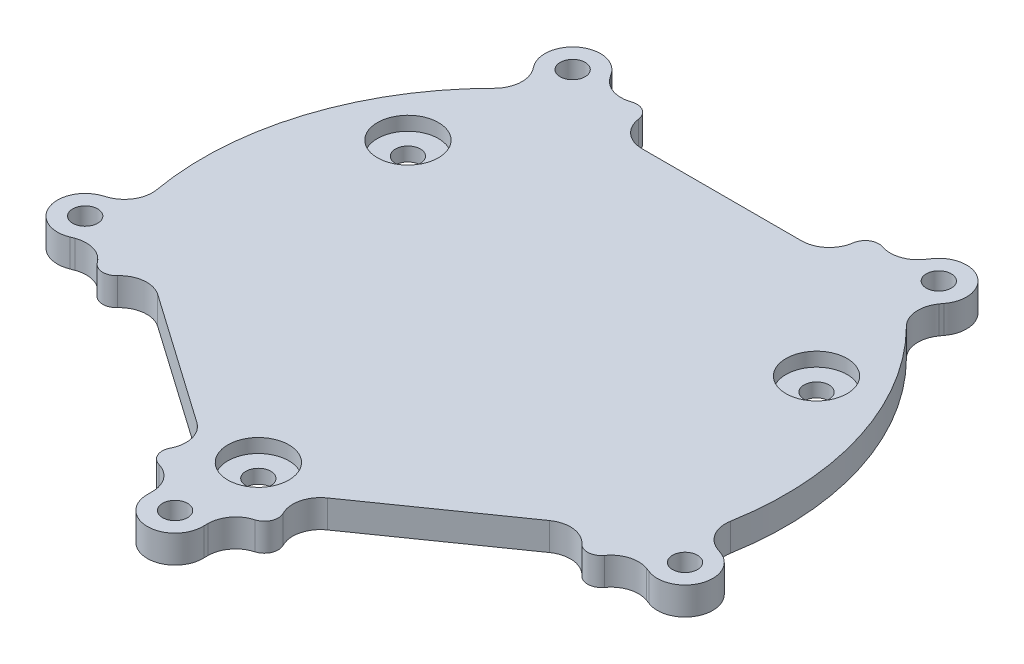
SolidWorks part; units mm, degrees
ref_plane "Plan de face" through (0, 0, 0) normal (0, 0, 1) x (1, 0, 0)
ref_plane "Plan de dessus" through (0, 0, 0) normal (0, 1, 0) x (1, 0, 0)
ref_plane "Plan de droite" through (0, 0, 0) normal (1, 0, 0) x (0, 0, -1)
sketch "Sketch1" plane through (0, 0, 0) normal (0, 1, 0) x (1, 0, 0)
  line L0 (0, 0) -> (0, 41) construction
  line L1 (0, 0) -> (-23.5166, -33.5852) construction
  line L2 (0, 0) -> (23.5166, -33.5852) construction
  line L3 (-39.3263, -22.5152) -> (-7.707, -44.6553)
  line L4 (7.707, -44.6553) -> (39.3263, -22.5152)
  line L5 (-19.3, 41) -> (19.3, 41)
  line L6 (-19.3, 41) -> (-19.3, 48.8238)
  line L8 (19.3, 41) -> (19.3, 48.8238)
  line L9 (7.707, -44.6553) -> (12.1945, -51.0641)
  line L11 (39.3263, -22.5152) -> (43.8138, -28.9241)
  line L12 (-7.707, -44.6553) -> (-12.1945, -51.0641)
  line L13 (-39.3263, -22.5152) -> (-43.8138, -28.9241)
  line L14 (0, 0) -> (0, -42.5) construction
  line L15 (0, 0) -> (-36.8061, 21.25) construction
  line L16 (0, 0) -> (36.8061, 21.25) construction
  arc A0 (-19.3, 48.8238) -> (-43.8138, -28.9241) centre (0, 0) ccw
  arc A1 (43.8138, -28.9241) -> (19.3, 48.8238) centre (0, 0) ccw
  circle A3 centre (-36.8061, 21.25) radius 2.25 construction
  circle A4 centre (36.8061, 21.25) radius 2.25 construction
  circle A6 centre (0, -42.5) radius 2.25 construction
  arc A7 (-12.1945, -51.0641) -> (12.1945, -51.0641) centre (0, 0) ccw
  circle A8 centre (-36.8061, 21.25) radius 5.5
  circle A9 centre (36.8061, 21.25) radius 5.5
  circle A10 centre (0, -42.5) radius 5.5
  point P25 (23.5166, -33.5852)
  point P26 (-23.5166, -33.5852)
  dimension "D1" = 105
  dimension "D5" = 35
  dimension "D6" = 38.6
  dimension "D10" = 4.5
  dimension "D4" = 11
  dimension "D9" = 42.5
  dimension "D2" = 35
  dimension "D3" = 41
  dimension "D7" = 120
  dimension "D8" = 120
extrude "Boss-Extrude1" add sketch "Sketch1" along normal blind 5 contours L4 A0 L5 L3 | A8 | A9 | A10 region at (0, 0, -1.6314) region at (-36.8061, 0, -21.25) region at (36.8061, 0, -21.25) region at (0, 0, 42.5)
extrude "Enlèv. mat.-Extru.3" cut sketch "Sketch1<3>" against normal blind 2.5 from surface contours A8 | A9 | A10 region at (-36.8061, 0, -21.25) region at (36.8061, 0, -21.25) region at (0, 0, 42.5) starting at face at (0, 5, 8.7026)
sketch "Sketch1<3>" plane through (0, 0, 0) normal (0, 1, 0) x (1, 0, 0) same geometry as "Sketch1"
sketch "Esquisse4" plane through (0, 5, 0) normal (0, 1, 0) x (1, 0, 0)
  point P0 (0, -42.5)
  point P3 (36.8061, 21.25)
  point P6 (-36.8061, 21.25)
hole_wizard "M4 Clearance Hole1" positions "Esquisse4" profile "Esquisse3" hole size "M4" standard "ANSI Metric" end condition up to next
sketch "Esquisse3" plane through (0, 5, 42.5) normal (1, 0, 0) x (0, 0, 1)
  line L0 (0, 0) -> (0, 5)
  line L1 (0, 5) -> (2.25, 5)
  line L2 (2.25, 5) -> (2.25, 0)
  line L5 (2.25, 0) -> (0, 0)
  line L11 (0, -6.35) -> (0, 107.95) construction
  dimension "Thru Hole Dia." = 4.5
  dimension "Thru Hole Depth" = 5
fillet "Congé1" radius 2.5 6 edges at (19.3, 2.5, -48.8238) (-19.3, 2.5, -48.8238) (-43.8138, 2.5, 28.9241) (43.8138, 2.5, 28.9241) (12.1945, 2.5, 51.0641) (-12.1945, 2.5, 51.0641)
sketch "Esquisse5" plane through (0, 5, 0) normal (0, 1, 0) x (1, 0, 0)
  line L0 (0, 0) -> (0, -57.5) construction
  line L1 (0, 0) -> (54.0323, -19.6662) construction
  line L2 (0, 0) -> (32.9806, 47.1012) construction
  line L3 (0, 0) -> (-32.9806, 47.1012) construction
  line L4 (0, 0) -> (-54.0323, -19.6662) construction
  line L5 (-52.1196, -24.2858) -> (-47.4016, -22.5686)
  line L6 (-55.5365, -14.8978) -> (-50.8185, -13.1806)
  line L7 (-36.9478, 44.058) -> (-34.068, 39.9452)
  line L8 (-28.7641, 49.7883) -> (-25.8843, 45.6755)
  line L9 (36.9478, 44.058) -> (34.068, 39.9452)
  line L10 (28.7641, 49.7883) -> (25.8843, 45.6755)
  line L11 (52.1196, -24.2858) -> (47.4016, -22.5686)
  line L12 (55.5365, -14.8978) -> (50.8185, -13.1806)
  line L13 (4.9953, -57.2826) -> (4.9953, -52.2618)
  line L14 (-4.9953, -57.2826) -> (-4.9953, -52.2618)
  arc A0 (-4.9953, -57.2826) -> (-52.1196, -24.2858) centre (0, 0) ccw construction
  arc A1 (52.1196, -24.2858) -> (55.5365, -14.8978) centre (54.0323, -19.6662) ccw
  arc A2 (-4.9953, -57.2826) -> (4.9953, -57.2826) centre (0, -57.5) ccw
  arc A3 (-55.5365, -14.8978) -> (-52.1196, -24.2858) centre (-54.0323, -19.6662) ccw
  arc A4 (-28.7641, 49.7883) -> (-36.9478, 44.058) centre (-32.9806, 47.1012) ccw
  arc A5 (36.9478, 44.058) -> (28.7641, 49.7883) centre (32.9806, 47.1012) ccw
  arc A6 (-8.3495, -51.8318) -> (8.3495, -51.8318) centre (0, 0) ccw construction
  arc A7 (-22.89, 47.2472) -> (-45.8503, -25.5735) centre (0, 0) ccw construction
  arc A8 (45.8503, -25.5735) -> (22.89, 47.2472) centre (0, 0) ccw construction
  arc A9 (-8.3495, -51.8318) -> (8.3495, -51.8318) centre (0, 0) ccw construction
  arc A10 (47.4016, -22.5686) -> (50.8185, -13.1806) centre (0, 0) ccw
  arc A11 (34.068, 39.9452) -> (25.8843, 45.6755) centre (0, 0) ccw
  arc A12 (-25.8843, 45.6755) -> (-34.068, 39.9452) centre (0, 0) ccw
  arc A13 (-50.8185, -13.1806) -> (-47.4016, -22.5686) centre (0, 0) ccw
  arc A14 (-4.9953, -52.2618) -> (4.9953, -52.2618) centre (0, 0) ccw
  dimension "D1" = 70
  dimension "D5" = 10
  dimension "D2" = 70
  dimension "D3" = 75
  dimension "D4" = 75
extrude "Boss.-Extru.1" add sketch "Esquisse5" against normal up to surface (5 mm away) up to face at (0, 0, 44.75)
sketch "Esquisse8" plane through (0, 5, 0) normal (0, 1, 0) x (1, 0, 0)
  point P0 (0, -57.5)
  point P3 (54.0323, -19.6662)
  point P6 (32.9806, 47.1012)
  point P9 (-32.9806, 47.1012)
  point P12 (-54.0323, -19.6662)
hole_wizard "M4 Clearance Hole2" positions "Esquisse8" profile "Esquisse7" hole size "M4" standard "ANSI Metric" end condition up to next
sketch "Esquisse7" plane through (0, 5, 57.5) normal (1, 0, 0) x (0, 0, 1)
  line L0 (0, 0) -> (0, 5)
  line L1 (0, 5) -> (2.25, 5)
  line L2 (2.25, 5) -> (2.25, 0)
  line L5 (2.25, 0) -> (0, 0)
  line L11 (0, -6.35) -> (0, 107.95) construction
  dimension "Thru Hole Dia." = 4.5
  dimension "Thru Hole Depth" = 5
fillet "Congé2" radius 5 16 edges at (47.4016, 2.5, 22.5686) (50.8185, 2.5, 13.1806) (34.068, 2.5, -39.9452) (-34.068, 2.5, -39.9452) (-50.8185, 2.5, 13.1806) (-47.4016, 2.5, 22.5686) (4.9953, 2.5, 52.2618) (-4.9953, 2.5, 52.2618) (25.8843, 2.5, -45.6755) (-25.8843, 2.5, -45.6755) (-7.707, 2.5, 44.6553) (-39.3263, 2.5, 22.5152) (-19.3, 2.5, -41) (19.3, 2.5, -41) (39.3263, 2.5, 22.5152) (7.707, 2.5, 44.6553)
